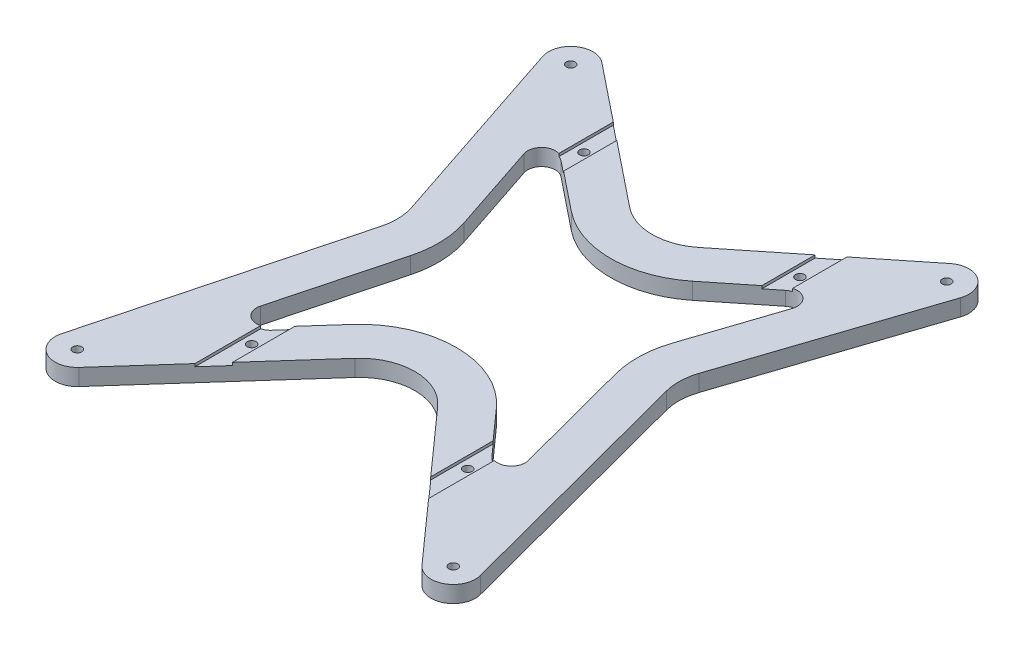
SolidWorks part; units mm, degrees
material "1060 Alloy"
ref_plane "Front Plane" through (0, 0, 0) normal (0, 0, 1) x (1, 0, 0)
ref_plane "Top Plane" through (0, 0, 0) normal (0, 1, 0) x (1, 0, 0)
ref_plane "Right Plane" through (0, 0, 0) normal (1, 0, 0) x (0, 0, -1)
sketch "Sketch1" plane through (0, 0, 0) normal (0, 1, 0) x (1, 0, 0)
  line L0 (-62.8826, 95.3407) -> (0, 45)
  line L1 (0, 45) -> (62.8826, 95.3407)
  line L2 (75.4732, 86.5701) -> (50, 10)
  line L3 (50, 10) -> (75.6173, -87.0538)
  line L4 (61.9117, -94.4202) -> (0, -25)
  line L5 (0, -25) -> (-61.9117, -94.4202)
  line L6 (-75.6173, -87.0538) -> (-50, 10)
  line L7 (-50, 10) -> (-75.4732, 86.5701)
  line L8 (-78.4889, 78.4889) -> (78.4889, -78.4889) construction
  line L9 (-42, 75) -> (-36, 75) construction
  line L10 (-42, 75) -> (-42, 55) construction
  line L11 (-42, 55) -> (-36, 55) construction
  line L12 (-36, 75) -> (-36, 55) construction
  line L13 (-42, 75) -> (-36, 55) construction
  line L14 (-42, 55) -> (-36, 75) construction
  line L15 (36, 75) -> (42, 75) construction
  line L16 (36, 75) -> (36, 55) construction
  line L17 (36, 55) -> (42, 55) construction
  line L18 (42, 75) -> (42, 55) construction
  line L19 (36, 75) -> (42, 55) construction
  line L20 (36, 55) -> (42, 75) construction
  line L21 (36, -45) -> (42, -45) construction
  line L22 (36, -45) -> (36, -65) construction
  line L23 (36, -65) -> (42, -65) construction
  line L24 (42, -45) -> (42, -65) construction
  line L25 (36, -45) -> (42, -65) construction
  line L26 (36, -65) -> (42, -45) construction
  line L27 (-42, -45) -> (-36, -45) construction
  line L28 (-42, -45) -> (-42, -65) construction
  line L29 (-42, -65) -> (-36, -65) construction
  line L30 (-36, -45) -> (-36, -65) construction
  line L31 (-42, -45) -> (-36, -65) construction
  line L32 (-42, -65) -> (-36, -45) construction
  line L33 (111, 45.9777) -> (45.9777, 111) construction
  line L34 (45.9777, 111) -> (-45.9777, 111) construction
  line L35 (-45.9777, 111) -> (-111, 45.9777) construction
  line L36 (-111, 45.9777) -> (-111, -45.9777) construction
  line L37 (-111, -45.9777) -> (-45.9777, -111) construction
  line L38 (-45.9777, -111) -> (45.9777, -111) construction
  line L39 (45.9777, -111) -> (111, -45.9777) construction
  line L40 (111, -45.9777) -> (111, 45.9777) construction
  line L41 (78.4889, 78.4889) -> (-78.4889, -78.4889) construction
  circle A0 centre (-67.8823, 89.0955) radius 1.6
  circle A1 centre (67.8823, 89.0955) radius 1.6
  circle A2 centre (-67.8823, -89.0955) radius 1.6
  circle A3 centre (67.8823, -89.0955) radius 1.6
  arc A4 (-62.8826, 95.3407) -> (-75.4732, 86.5701) centre (-67.8823, 89.0955) ccw
  arc A5 (62.8826, 95.3407) -> (75.4732, 86.5701) centre (67.8823, 89.0955) cw
  arc A6 (-75.6173, -87.0538) -> (-61.9117, -94.4202) centre (-67.8823, -89.0955) ccw
  arc A7 (75.6173, -87.0538) -> (61.9117, -94.4202) centre (67.8823, -89.0955) cw
  circle A8 centre (0, 0) radius 111 construction
  circle A9 centre (-39, 65) radius 1.6
  circle A10 centre (39, 65) radius 1.6
  circle A11 centre (39, -55) radius 1.6
  circle A12 centre (-39, -55) radius 1.6
  ellipse E0 centre (0, 10) end of major axis (50, 10) minor radius 35 construction
  dimension "D5" = 3.2
  dimension "D6" = 35
  dimension "D7" = 8
  dimension "D12" = 3.2
  dimension "D3" = 15
  dimension "D4" = 15
  dimension "D8" = 120
  dimension "D9" = 78
  dimension "D10" = 10
  dimension "D11" = 55
  dimension "D13" = 50
  dimension "D14" = 39
  dimension "D15" = 20
  dimension "D16" = 6
  dimension "D17" = 111
  dimension "D18" = 15
extrude "Boss-Extrude1" add sketch "Sketch1" along normal blind 6
fillet "Fillet1" radius 20 4 edges at (0, 3, -45) (-50, 3, -10) (0, 3, 25) (50, 3, -10)
sketch "Sketch2" plane through (0, 6, 0) normal (0, 1, 0) x (1, 0, 0)
  line L44 (-53.7612, 68.824) -> (-37.6483, 20.3901)
  line L45 (-37.0177, 0.4094) -> (-53.6562, -62.6272)
  line L46 (-53.6562, -62.6272) -> (-26.121, -31.7526)
  line L47 (26.121, -31.7526) -> (53.6562, -62.6272)
  line L48 (53.6562, -62.6272) -> (37.0177, 0.4094)
  line L49 (37.6483, 20.3901) -> (53.7612, 68.824)
  line L50 (53.7612, 68.824) -> (21.8735, 43.2963)
  line L51 (-21.8735, 43.2963) -> (-53.7612, 68.824)
  line L52 (-53.7612, 68.824) -> (-37.6483, 20.3901)
  line L53 (-37.0177, 0.4094) -> (-53.6562, -62.6272)
  line L54 (-53.6562, -62.6272) -> (-26.121, -31.7526)
  line L55 (26.121, -31.7526) -> (53.6562, -62.6272)
  line L56 (53.6562, -62.6272) -> (37.0177, 0.4094)
  line L57 (37.6483, 20.3901) -> (53.7612, 68.824)
  line L58 (53.7612, 68.824) -> (21.8735, 43.2963)
  line L59 (-21.8735, 43.2963) -> (-53.7612, 68.824)
  arc A40 (-37.0177, 0.4094) -> (-37.6483, 20.3901) centre (-70.8587, 9.3417) ccw
  arc A41 (26.121, -31.7526) -> (-26.121, -31.7526) centre (0, -55.0484) ccw
  arc A42 (37.6483, 20.3901) -> (37.0177, 0.4094) centre (70.8587, 9.3417) ccw
  arc A43 (-21.8735, 43.2963) -> (21.8735, 43.2963) centre (0, 70.6194) ccw
  arc A44 (-37.0177, 0.4094) -> (-37.6483, 20.3901) centre (-70.8587, 9.3417) ccw
  arc A45 (26.121, -31.7526) -> (-26.121, -31.7526) centre (0, -55.0484) ccw
  arc A46 (37.6483, 20.3901) -> (37.0177, 0.4094) centre (70.8587, 9.3417) ccw
  arc A47 (-21.8735, 43.2963) -> (21.8735, 43.2963) centre (0, 70.6194) ccw
  dimension "D1" = 15
extrude "Cut-Extrude1" cut sketch "Sketch2" against normal up to next
fillet "Fillet4" radius 5 4 edges at (53.6562, 3, 62.6272) (-53.6562, 3, 62.6272) (53.7612, 3, -68.824) (-53.7612, 3, -68.824)
sketch "Sketch6" plane through (0, 6, 0) normal (0, 1, 0) x (1, 0, 0)
  line L0 (-12.4991, 55.0062) -> (-62.8826, 95.3407) construction
  line L1 (-42.2, -39) -> (-35.8, -39)
  line L2 (-42.2, -39) -> (-42.2, -72.3179)
  line L3 (-42.2, -72.3179) -> (-35.8, -72.3179)
  line L4 (-35.8, -39) -> (-35.8, -72.3179)
  line L5 (35.8, -39) -> (42.2, -39)
  line L6 (35.8, -39) -> (35.8, -72.3179)
  line L7 (35.8, -72.3179) -> (42.2, -72.3179)
  line L8 (42.2, -39) -> (42.2, -72.3179)
  line L9 (35.8, 53) -> (42.2, 53)
  line L10 (35.8, 53) -> (35.8, 78.7833)
  line L11 (35.8, 78.7833) -> (42.2, 78.7833)
  line L12 (42.2, 53) -> (42.2, 78.7833)
  line L13 (-42.2, 53) -> (-35.8, 53)
  line L14 (-42.2, 53) -> (-42.2, 78.7833)
  line L15 (-42.2, 78.7833) -> (-35.8, 78.7833)
  line L16 (-35.8, 53) -> (-35.8, 78.7833)
  line L17 (62.8826, 95.3407) -> (12.4991, 55.0062) construction
  line L18 (14.9263, -41.7365) -> (61.9117, -94.4202) construction
  line L19 (-61.9117, -94.4202) -> (-14.9263, -41.7365) construction
  circle A0 centre (-39, -55) radius 1.6 construction
  circle A1 centre (39, -55) radius 1.6 construction
  circle A2 centre (-39, 65) radius 1.6 construction
  dimension "D2" = 3.2
  dimension "D3" = 3.2
  dimension "D5" = 12
  dimension "D1" = 6.4
  dimension "D4" = 16
extrude "Cut-Extrude2" cut sketch "Sketch6" against normal blind 1
sketch "Sketch7" plane through (0, 0, 0) normal (0, -1, 0) x (1, 0, 0)
  circle A0 centre (-39, 55) radius 3.1
  circle A1 centre (39, 55) radius 3.1
  circle A2 centre (-39, -65) radius 3.1
  circle A3 centre (39, -65) radius 3.1
  dimension "D1" = 6.2
extrude "Cut-Extrude3" cut sketch "Sketch7" against normal blind 1
chamfer "Chamfer1" distance 1.5 angle 45 4 edges at (39, 1, -66.6) (-39, 1, -66.6) (39, 1, 53.4) (-39, 1, 53.4)
equation "\"D14@Sketch1\"=\"D9@Sketch1\"/2"
